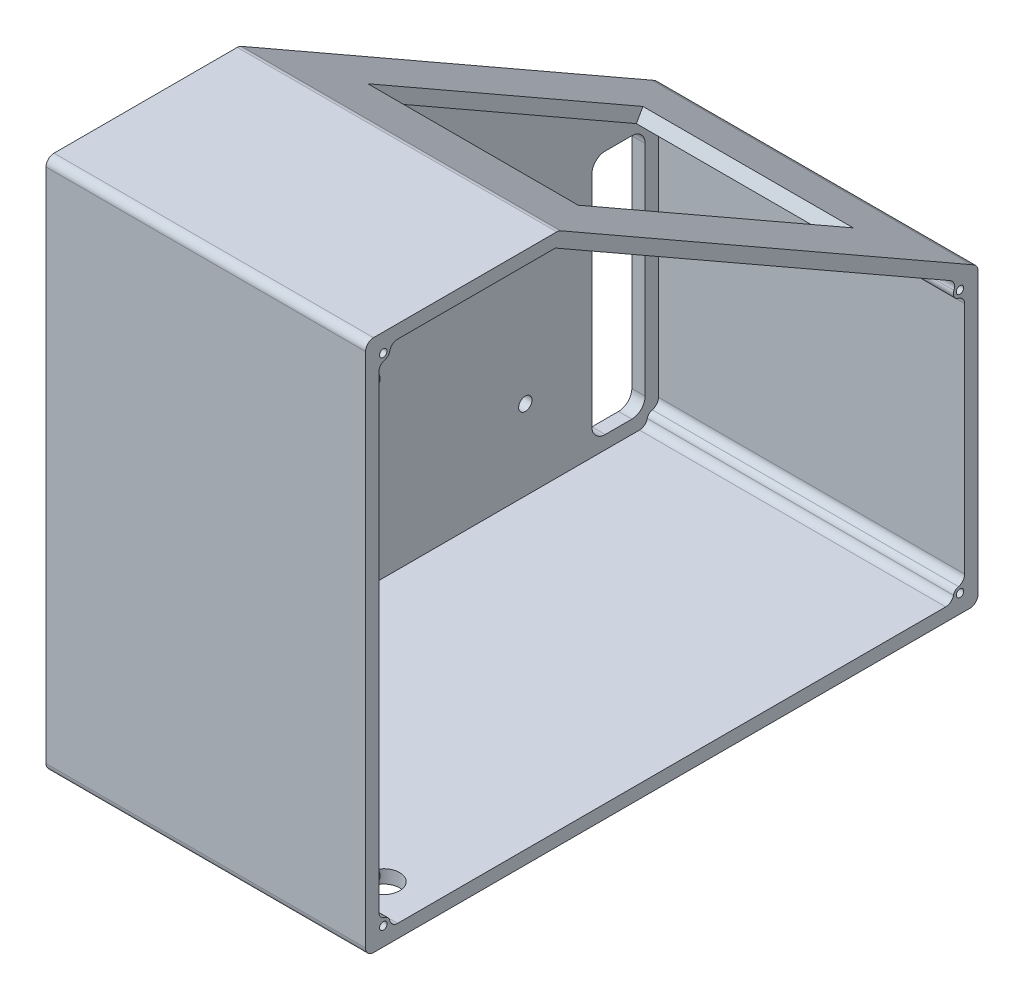
SolidWorks part; units mm, degrees
ref_plane "Front Plane" through (0, 0, 0) normal (0, 0, 1) x (1, 0, 0)
ref_plane "Top Plane" through (0, 0, 0) normal (0, 1, 0) x (1, 0, 0)
ref_plane "Right Plane" through (0, 0, 0) normal (1, 0, 0) x (0, 0, -1)
sketch "Sketch1" plane through (0, 0, 0) normal (1, 0, 0) x (0, 0, -1)
  line L0 (-116.6039, 100.2005) -> (-43.9901, 100.2005)
  line L1 (-43.9901, 100.2005) -> (110.8784, 11.7075)
  line L2 (110.8784, 11.7075) -> (113.3961, 10.2676)
  line L3 (113.3961, 10.2676) -> (113.3961, -99.7995)
  line L4 (113.3961, -99.7995) -> (-116.6039, -99.7995)
  line L5 (-116.6039, -99.7995) -> (-116.6039, 100.2005)
  dimension "D1" = 178.3683
  dimension "D2" = 200
  dimension "D3" = 230
  dimension "D4" = 72.6137
extrude "Boss-Extrude1" add sketch "Sketch1" along normal blind 120 contours L0 L1 L2 L3 L4 L5
sketch "Sketch2" plane through (120, 0, 0) normal (1, 0, 0) x (0, 0, -1)
  line L12 (-111.6039, 95.2005) -> (-111.6039, -94.7995)
  line L13 (-111.6039, -94.7995) -> (108.3961, -94.7995)
  line L14 (108.3961, -94.7995) -> (108.3961, 7.3672)
  line L15 (108.3961, 7.3672) -> (-45.3179, 95.2005)
  line L16 (-45.3179, 95.2005) -> (-111.6039, 95.2005)
  line L17 (-111.6039, 95.2005) -> (-111.6039, -94.7995)
  line L18 (-111.6039, -94.7995) -> (108.3961, -94.7995)
  line L19 (108.3961, -94.7995) -> (108.3961, 7.3672)
  line L20 (108.3961, 7.3672) -> (-45.3179, 95.2005)
  line L21 (-45.3179, 95.2005) -> (-111.6039, 95.2005)
  dimension "D1" = 5
extrude "Cut-Extrude1" cut sketch "Sketch2" against normal blind 115
sketch "Sketch3" plane through (5, 0, 0) normal (1, 0, 0) x (0, 0, -1)
  line L0 (108.3961, -94.7995) -> (108.3961, 7.3672) construction
  line L1 (98.3961, 2.3672) -> (88.3961, 2.3672)
  line L2 (103.3961, -2.6328) -> (103.3961, -84.7995)
  line L3 (98.3961, -89.7995) -> (88.3961, -89.7995)
  line L4 (83.3961, -2.6328) -> (83.3961, -84.7995)
  line L5 (-111.6039, -94.7995) -> (108.3961, -94.7995) construction
  arc A0 (88.3961, -89.7995) -> (83.3961, -84.7995) centre (88.3961, -84.7995) cw
  arc A1 (103.3961, -84.7995) -> (98.3961, -89.7995) centre (98.3961, -84.7995) cw
  arc A2 (88.3961, 2.3672) -> (83.3961, -2.6328) centre (88.3961, -2.6328) ccw
  arc A3 (98.3961, 2.3672) -> (103.3961, -2.6328) centre (98.3961, -2.6328) cw
  dimension "D5" = 5
  dimension "D1" = 5
  dimension "D2" = 5
  dimension "D3" = 5
  dimension "D4" = 20
extrude "Cut-Extrude2" cut sketch "Sketch3" against normal blind 115 contours L2 A1 L3 A0 L4 A2 L1 A3
fillet "Fillet1" radius 3 5 edges at (60, 100.2005, 43.9901) (60, 10.2676, -113.3961) (60, -99.7995, -113.3961) (60, -99.7995, 116.6039) (60, 100.2005, 116.6039)
sketch "Sketch4" plane through (5, 0, 0) normal (1, 0, 0) x (0, 0, -1)
  line L0 (-109.9293, -95.4433) -> (110.3961, -95.4433) construction
  line L2 (108.3961, -94.7995) -> (104.8606, -91.264) construction
  line L3 (108.3961, 7.3672) -> (102.3394, 1.3104) construction
  circle A0 centre (-109.9526, 93.3234) radius 2.5
  circle A1 centre (-109.9526, 93.3234) radius 1.4
  circle A2 centre (-109.9293, -92.9433) radius 2.5
  circle A3 centre (-109.9293, -92.9433) radius 1.4
  circle A6 centre (106.6283, -93.0317) radius 2.5
  circle A7 centre (106.6283, -93.0317) radius 1.4
  circle A8 centre (106.6283, 5.5994) radius 2.5
  circle A9 centre (106.6283, 5.5994) radius 1.4
  dimension "D1" = 5
  dimension "D2" = 2.8
  dimension "D3" = 5
  dimension "D4" = 2.8
  dimension "D5" = 5
  dimension "D6" = 2.8
  dimension "D7" = 5
  dimension "D8" = 2.8
extrude "Boss-Extrude2" add sketch "Sketch4" along normal blind 115
extrude "Boss-Extrude3" add sketch "Sketch4<2>" along normal blind 105 contours A1 | A7 | A9 | A3 region at (5, 93.3234, 109.9526) region at (5, -93.0317, -106.6283) region at (5, 5.5994, -106.6283)
sketch "Sketch4<2>" plane through (5, 0, 0) normal (1, 0, 0) x (0, 0, -1) same geometry as "Sketch4"
fillet "Fillet2" radius 3 8 edges at (62.5, 3.8316, -108.3961) (62.5, 8.0199, -107.2538) (62.5, -91.264, -108.3961) (62.5, -94.7995, -104.8606) (62.5, -91.087, 111.6039) (62.5, -94.7995, 108.2546) (62.5, 91.4464, 111.6039) (62.5, 95.2005, 108.3013)
sketch "Sketch6" plane through (0, 56.5879, -32.3347) normal (0, 0.8683, -0.4961) x (1, 0, 0)
  line L0 (20.5, 63.0557) -> (99.5, 63.0557)
  line L1 (20.5, 63.0557) -> (20.5, -55.9443)
  line L2 (20.5, -55.9443) -> (99.5, -55.9443)
  line L3 (99.5, 63.0557) -> (99.5, -55.9443)
  line L4 (120, -87.1098) -> (120, 90.4619) construction
  line L5 (120, 90.4619) -> (0, 90.4619) construction
  line L6 (0, -87.1098) -> (0, 90.4619) construction
  line L7 (0, -87.1098) -> (120, -87.1098) construction
  point P4 (120, 90.4619)
  point P11 (0, 94.2257)
  dimension "D1" = 79
  dimension "D2" = 119
  dimension "D3" = 120
  dimension "D4" = 20.5
  dimension "D5" = 181.3355
  dimension "D6" = 31.17
extrude "Cut-Extrude3" cut sketch "Sketch6" against normal blind 108
sketch "Sketch9" plane through (5, 0, 0) normal (1, 0, 0) x (0, 0, -1)
  line L5 (58.3961, 1.3853) -> (58.3961, -64.7995)
  line L10 (78.3961, -64.7995) -> (78.3961, -10.5)
  line L11 (78.0248, -9.8307) -> (-53.2846, 65.2005)
  line L12 (-53.2846, 65.2005) -> (-81.6039, 65.2005)
  line L13 (-81.6039, 65.2005) -> (-81.6039, -64.7995)
  line L14 (-81.6039, -64.7995) -> (78.3961, -64.7995)
  line L16 (60.5667, 0.145) -> (-53.2846, 65.2005)
  line L17 (-53.2846, 65.2005) -> (-81.6039, 65.2005)
  line L18 (-81.6039, 65.2005) -> (-81.6039, -64.7995)
  line L19 (-81.6039, -64.7995) -> (60.8961, -64.7995)
  circle A12 centre (-81.6039, 65.2005) radius 2.5
  circle A13 centre (-81.6039, -64.7995) radius 2.5
  circle A14 centre (58.3961, 1.3853) radius 2.5
  circle A15 centre (58.3961, -64.7995) radius 2.5
  arc A24 (78.0248, -9.8307) -> (78.3961, -10.5) centre (106.6283, 5.5994) ccw
  arc A25 (78.0248, -9.8307) -> (78.3961, -10.5) centre (106.6283, 5.5994) ccw
  dimension "D2" = 5
  dimension "D1" = 30
extrude "Cut-Extrude4" cut sketch "Sketch9" against normal blind 5 contours L18 A13 L19 | L19 A13 L18 | L16 A14 | L16 A14 L5 | L5 A14 L16 | L5 A15 L19 | L19 A15 L5 | L19 A15 | A12 | A14 region at (5, 0.0093, -59.1946) region at (5, 2.3066, -58.9225) region at (5, 0.6929, -57.203) region at (5, -63.7385, -59.4571) region at (5, -63.7385, -57.3351) region at (5, -65.8605, -58.3961) region at (5, -65.1532, 81.9576) region at (5, -63.7385, 80.5429)
sketch "Sketch10" plane through (0, 0, 111.6039) normal (0, 0, -1) x (-1, 0, 0)
  line L0 (-120, 87.9914) -> (-120, -87.6054) construction
  line L1 (-113, 80.9914) -> (-12, 80.9914)
  line L2 (-113, 80.9914) -> (-113, -80.6054)
  line L3 (-113, -80.6054) -> (-12, -80.6054)
  line L4 (-12, 80.9914) -> (-12, -80.6054)
  line L5 (-5, 87.9914) -> (-5, -87.6054) construction
  line L6 (-5, 87.9914) -> (-120, 87.9914) construction
  line L7 (-120, -87.6054) -> (-5, -87.6054) construction
  line L9 (-113, 5.1512) -> (-12, 5.1512)
  line L10 (-113, 5.1512) -> (-113, -7.9147)
  line L11 (-113, -7.9147) -> (-12, -7.9147)
  line L12 (-12, 5.1512) -> (-12, -7.9147)
  circle A0 centre (-113, 80.9914) radius 2.5
  circle A1 centre (-12, 80.9914) radius 2.5
  circle A2 centre (-113, -80.6054) radius 2.5
  circle A3 centre (-12, -80.6054) radius 2.5
  circle A4 centre (-113, -80.6054) radius 1.4
  circle A5 centre (-12, -80.6054) radius 1.4
  circle A6 centre (-12, 80.9914) radius 1.4
  circle A7 centre (-113, 80.9914) radius 1.4
  dimension "D5" = 5
  dimension "D6" = 2.8
  dimension "D1" = 7
  dimension "D2" = 7
  dimension "D3" = 7
  dimension "D4" = 7
extrude "Boss-Extrude4" add sketch "Sketch10" along normal blind 5 contours L2 L11 L4 L9 | A4 L2 A2 L3 | A4 L3 A2 L2 | A5 L4 A3 L3 | A5 L3 A3 L4 | A6 L4 A1 L1 | A6 L1 A1 L4 | A7 L1 A0 L2 | A7 L2 A0 L1 region at (114.0399, 82.0313, 111.6039) region at (111.7257, 79.717, 111.6039) region at (12, 83.4207, 111.6039) region at (13.2743, 79.717, 111.6039) region at (62.5, -1.3817, 111.6039) region at (111.7257, -79.331, 111.6039) region at (113.0707, -78.6554, 111.6039) region at (10.2822, -78.8876, 111.6039) region at (13.2743, -79.331, 111.6039)
sketch "Sketch11" plane through (0, -99.7995, 0) normal (0, -1, 0) x (1, 0, 0)
  line L0 (120, 113.6039) -> (0, 113.6039) construction
  circle A0 centre (103.8439, 93.6039) radius 5.95
  circle A1 centre (78.5451, 93.6039) radius 5.95
  dimension "D1" = 11.9
  dimension "D3" = 11.9
  dimension "D2" = 20
extrude "Cut-Extrude5" cut sketch "Sketch11" against normal blind 5
sketch "Sketch12" plane through (0, 0, 111.6039) normal (0, 0, -1) x (-1, 0, 0)
  line L0 (-5, 87.9914) -> (-120, 87.9914) construction
  line L1 (-119, 86.9914) -> (-6, 86.9914)
  line L2 (-119, 86.9914) -> (-119, -86.6054)
  line L3 (-119, -86.6054) -> (-6, -86.6054)
  line L4 (-6, 86.9914) -> (-6, -86.6054)
  line L5 (-120, 87.9914) -> (-120, -87.6054) construction
  line L6 (-120, -87.6054) -> (-5, -87.6054) construction
  line L7 (-5, 87.9914) -> (-5, -87.6054) construction
  circle A0 centre (-113, 80.9914) radius 1.4
  circle A1 centre (-12, 80.9914) radius 1.4
  circle A2 centre (-12, -80.6054) radius 1.4
  circle A3 centre (-113, -80.6054) radius 1.4
  dimension "D1" = 1
  dimension "D2" = 1
  dimension "D3" = 1
  dimension "D4" = 1
